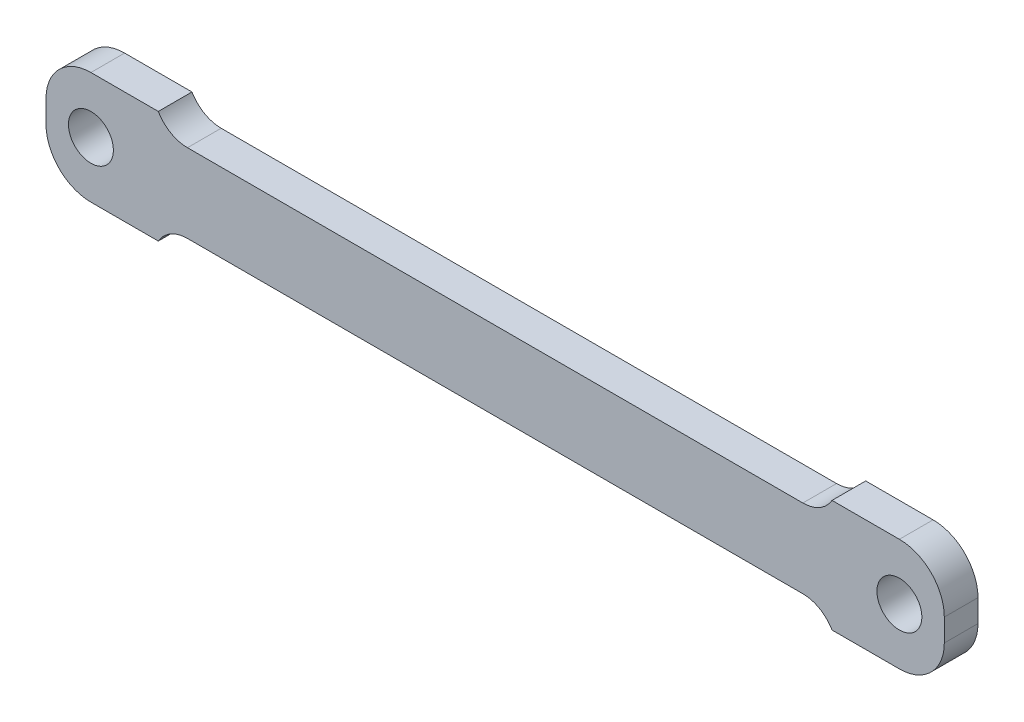
SolidWorks part; units mm, degrees
ref_plane "Front Plane" through (0, 0, 0) normal (0, 0, 1) x (1, 0, 0)
ref_plane "Top Plane" through (0, 0, 0) normal (0, 1, 0) x (1, 0, 0)
ref_plane "Right Plane" through (0, 0, 0) normal (1, 0, 0) x (0, 0, -1)
sketch "Sketch1" plane through (0, 0, 0) normal (0, 0, 1) x (1, 0, 0)
  line L1 (-18, 2.5) -> (18, 2.5)
  line L2 (-20, 0.5) -> (-20, -0.5)
  line L3 (-18, -2.5) -> (18, -2.5)
  line L4 (20, 0.5) -> (20, -0.5)
  line L5 (-20, 2.5) -> (20, -2.5) construction
  line L6 (-20, -2.5) -> (20, 2.5) construction
  circle A0 centre (18, 0) radius 1
  circle A1 centre (-18, 0) radius 1
  arc A2 (-20, -0.5) -> (-18, -2.5) centre (-18, -0.5) ccw
  arc A3 (-18, 2.5) -> (-20, 0.5) centre (-18, 0.5) ccw
  arc A4 (18, -2.5) -> (20, -0.5) centre (18, -0.5) ccw
  arc A5 (18, 2.5) -> (20, 0.5) centre (18, 0.5) cw
  point P0 (0, 0)
  point P10 (20, 0)
  point P11 (-20, 0)
  dimension "D3" = 2
  dimension "D4" = 2
  dimension "D7" = 2
  dimension "D1" = 5
  dimension "D2" = 40
  dimension "D5" = 2
  dimension "D6" = 2
extrude "Boss-Extrude1" add sketch "Sketch1" along normal blind 1.5
sketch "Sketch2" plane through (0, 0, 0) normal (0, 0, -1) x (-1, 0, 0)
  line L0 (-18, 2.5) -> (18, 2.5) construction
  line L1 (-15, 3.25) -> (15, 3.25)
  line L2 (-15, 3.25) -> (-15, 1.75)
  line L3 (-15, 1.75) -> (15, 1.75)
  line L4 (15, 3.25) -> (15, 1.75)
  line L5 (-15, 3.25) -> (15, 1.75) construction
  line L6 (-15, 1.75) -> (15, 3.25) construction
  line L7 (18, -2.5) -> (-18, -2.5) construction
  line L8 (-15, -1.75) -> (15, -1.75)
  line L9 (-15, -1.75) -> (-15, -3.25)
  line L10 (-15, -3.25) -> (15, -3.25)
  line L11 (15, -1.75) -> (15, -3.25)
  line L12 (-15, -1.75) -> (15, -3.25) construction
  line L13 (-15, -3.25) -> (15, -1.75) construction
  point P0 (0, 2.5)
  point P7 (0, -2.5)
  dimension "D1" = 30
  dimension "D2" = 30
  dimension "D3" = 1.5
  dimension "D4" = 1.5
extrude "Cut-Extrude1" cut sketch "Sketch2" against normal through all
fillet "Fillet1" radius 1.5 4 edges at (15, 1.75, 0.75) (-15, -1.75, 0.75) (15, -1.75, 0.75) (-15, 1.75, 0.75)
